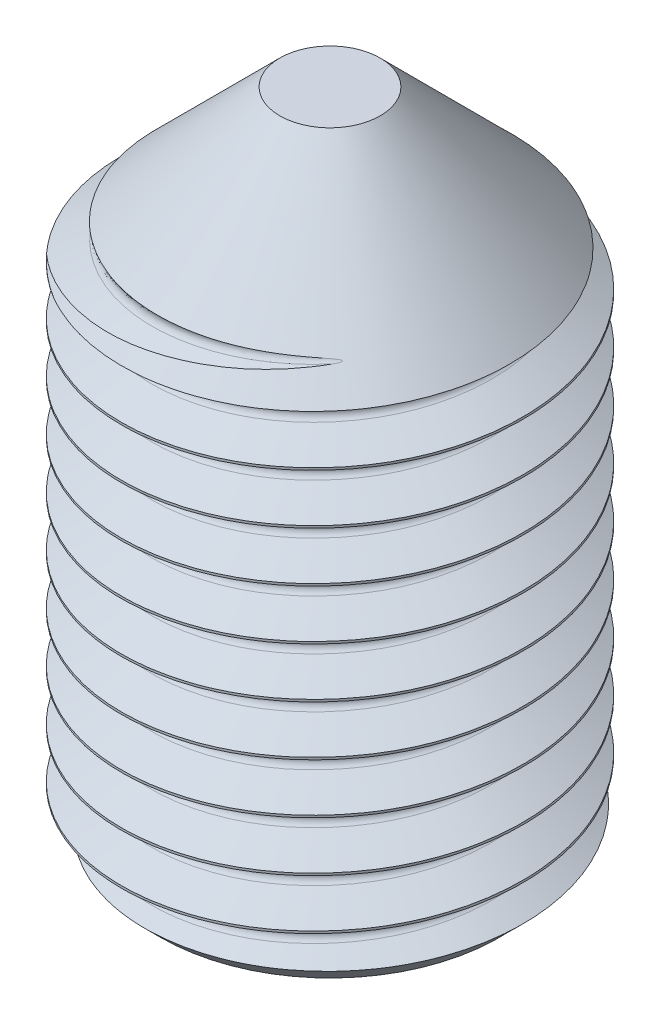
SolidWorks part; units mm, degrees
ref_plane "Front Plane" through (0, 0, 0) normal (0, 0, 1) x (1, 0, 0)
ref_plane "Top Plane" through (0, 0, 0) normal (0, 1, 0) x (1, 0, 0)
ref_plane "Right Plane" through (0, 0, 0) normal (1, 0, 0) x (0, 0, -1)
sketch "Sketch1" plane through (0, 0, 0) normal (0, 1, 0) x (1, 0, 0)
  circle A0 centre (0, 0) radius 8
  dimension "D1" = 16
extrude "Boss-Extrude1" add sketch "Sketch1" along normal mid plane 26
sketch "Sketch2" plane through (0, 0, 0) normal (0, 0, 1) x (1, 0, 0)
  line L0 (2, 13) -> (13.6082, 1.3918)
  line L1 (13.6082, 1.3918) -> (13.6082, -6.1418)
  line L2 (13.6082, -6.1418) -> (6.75, -13)
  line L3 (6.75, -13) -> (6.75, -17.7518)
  line L4 (6.75, -17.7518) -> (25.8792, -17.7518)
  line L5 (25.8792, -17.7518) -> (25.8792, 20.864)
  line L6 (25.8792, 20.864) -> (2, 20.864)
  line L7 (2, 20.864) -> (2, 13)
  line L8 (0, 0) -> (0, -3.1523) construction
  line L9 (8, 13) -> (-8, 13) construction
  line L10 (-8, -13) -> (8, -13) construction
  dimension "D1" = 4
  dimension "D2" = 13.5
  dimension "D3" = 135
  dimension "D4" = 135
revolve "Cut-Revolve1" cut sketch "Sketch2" angle 360 about L8
sketch "Sketch3" plane through (0, -13, 0) normal (0, -1, 0) x (1, 0, 0)
  line L1 (4.085, -2.3585) -> (4.085, 2.3585)
  line L2 (4.085, 2.3585) -> (0, 4.717)
  line L3 (0, 4.717) -> (-4.085, 2.3585)
  line L4 (-4.085, 2.3585) -> (-4.085, -2.3585)
  line L5 (-4.085, -2.3585) -> (0, -4.717)
  line L6 (0, -4.717) -> (4.085, -2.3585)
  circle A0 centre (0, 0) radius 4.085 construction
  dimension "D1" = 8.17
extrude "Cut-Extrude1" cut sketch "Sketch3" against normal blind 8
sketch "Sketch4" plane through (0, -13, 0) normal (0, -1, 0) x (1, 0, 0)
  circle A0 centre (0, 0) radius 8 construction
  circle A1 centre (0, 0) radius 8
curve "Helix/Spiral1" pitch 2 height 29 turns 14.5
sketch "Sketch5" plane through (0, 0, 0) normal (0, 0, 1) x (1, 0, 0)
  line L1 (8.0674, -12.2856) -> (6.7769, -13.0306)
  line L2 (6.7769, -13.5305) -> (8.0674, -14.2756)
  line L3 (8.0674, -14.2756) -> (8.0674, -12.2856)
  circle A0 centre (7.4929, -13.2806) radius 0.5745 construction
  arc A1 (6.7769, -13.0306) -> (6.7769, -13.5305) centre (6.9212, -13.2806) ccw
  dimension "D2" = 0.2886
  dimension "D1" = 1.99
sweep "Cut-Sweep1" cut profiles "Sketch5" path "Helix/Spiral1" align with end faces yes
sketch "Sketch6" plane through (0, -13, 0) normal (0, -1, 0) x (1, 0, 0)
  circle A0 centre (0, 0) radius 4.717
extrude "Cut-Extrude2" cut sketch "Sketch6" against normal blind 1.5 draft 75
